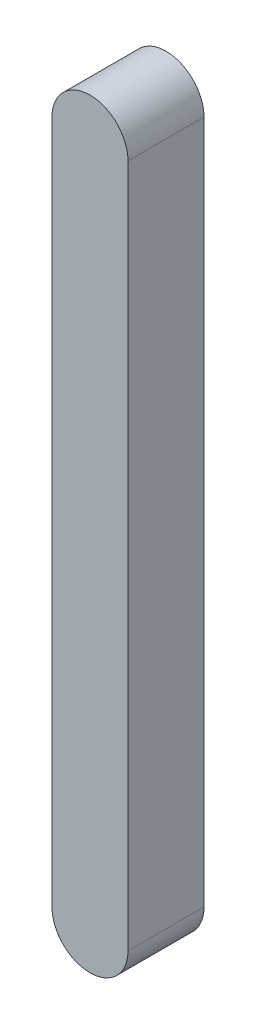
SolidWorks part; units mm, degrees
ref_plane "Plan de face" through (0, 0, 0) normal (0, 0, 1) x (1, 0, 0)
ref_plane "Plan de dessus" through (0, 0, 0) normal (0, 1, 0) x (1, 0, 0)
ref_plane "Plan de droite" through (0, 0, 0) normal (1, 0, 0) x (0, 0, -1)
sketch "Esquisse1" plane through (0, 0, 0) normal (0, 1, 0) x (1, 0, 0)
  line L1 (-12.5, 12.5) -> (12.5, 12.5)
  line L2 (-12.5, 12.5) -> (-12.5, -12.5)
  line L3 (-12.5, -12.5) -> (12.5, -12.5)
  line L4 (12.5, 12.5) -> (12.5, -12.5)
  dimension "D1" = 25
  dimension "D2" = 12.5
  dimension "D3" = 12.5
extrude "Boss.-Extru.1" add sketch "Esquisse1" along normal blind 225
sketch "Esquisse2" plane through (0, 0, 12.5) normal (0, 0, 1) x (1, 0, 0)
  line L0 (-12.5, 225) -> (12.5, 225) construction
  line L1 (-12.5, 225) -> (12.5, 225)
  arc A0 (12.5, 225) -> (-12.5, 225) centre (0, 225) ccw
  dimension "D1" = 12.5
extrude "Boss.-Extru.2" add sketch "Esquisse2" against normal up to surface (25 mm away) up to face at (0, 112.5, -12.5)
sketch "Esquisse3" plane through (0, 0, 12.5) normal (0, 0, 1) x (1, 0, 0)
  line L0 (-12.5, 0) -> (12.5, 0) construction
  line L1 (-12.5, 0) -> (12.5, 0)
  arc A0 (-12.5, 0) -> (12.5, 0) centre (0, 0) ccw
extrude "Boss.-Extru.3" add sketch "Esquisse3" against normal up to surface (25 mm away) up to face at (0, 115.625, -12.5)
sketch "Esquisse4" plane through (0, 0, -12.5) normal (0, 0, -1) x (-1, 0, 0)
  point P0 (0, 225)
sketch "Esquisse5" plane through (0, 0, -12.5) normal (0, 0, -1) x (-1, 0, 0)
  point P0 (0, 0)
